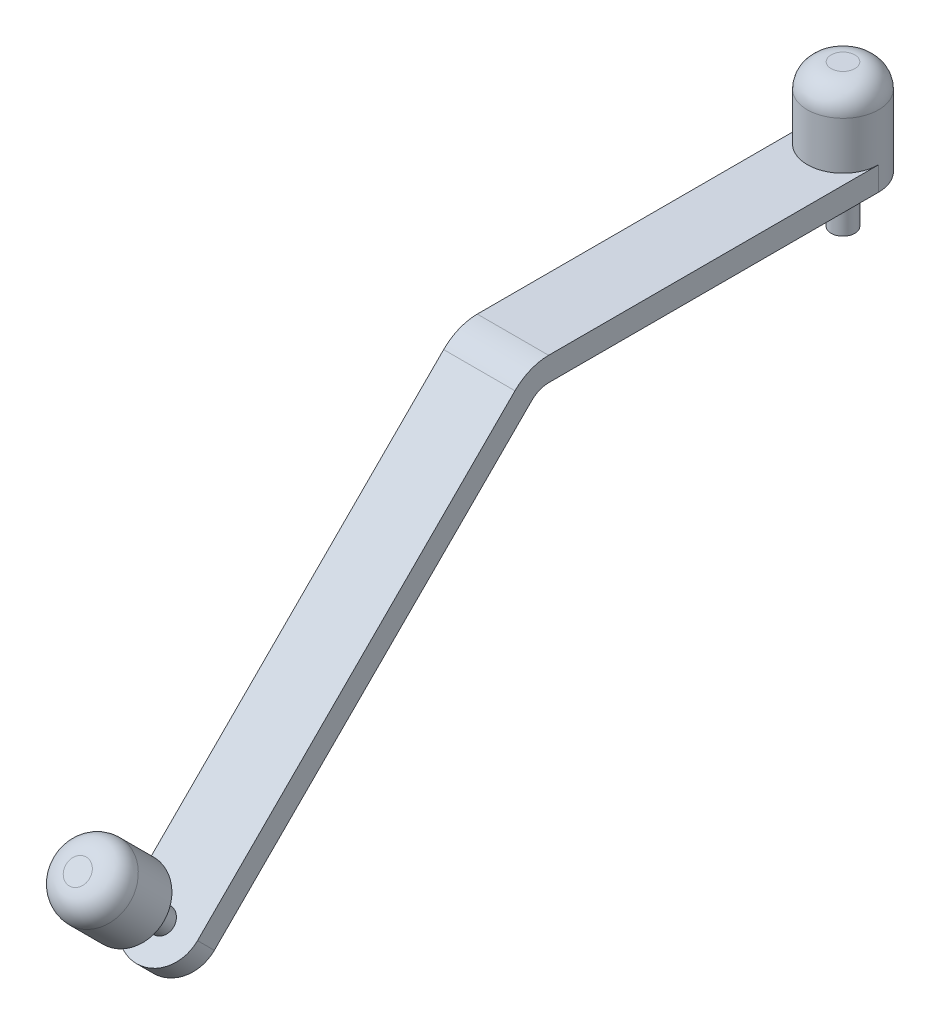
SolidWorks part; units mm, degrees
ref_plane "Front Plane" through (0, 0, 0) normal (0, 0, 1) x (1, 0, 0)
ref_plane "Top Plane" through (0, 0, 0) normal (0, 1, 0) x (1, 0, 0)
ref_plane "Right Plane" through (0, 0, 0) normal (1, 0, 0) x (0, 0, -1)
sketch "Sketch1" plane through (0, 0, 0) normal (1, 0, 0) x (0, 0, -1)
  line L0 (-80, 0) -> (-228.4924, -148.4924)
  line L1 (-80, -5) -> (80, -5)
  line L2 (-80, -5) -> (-80, 5)
  line L3 (-80, 5) -> (80, 5)
  line L4 (80, -5) -> (80, 5)
  line L5 (-80, -5) -> (80, 5) construction
  line L6 (-80, 5) -> (80, -5) construction
  line L7 (-232.028, -144.9569) -> (-83.5355, 3.5355)
  line L8 (-232.028, -144.9569) -> (-224.9569, -152.028)
  line L9 (-83.5355, 3.5355) -> (-76.4645, -3.5355)
  line L10 (-224.9569, -152.028) -> (-76.4645, -3.5355)
  line L11 (-232.028, -144.9569) -> (-76.4645, -3.5355) construction
  line L12 (-83.5355, 3.5355) -> (-224.9569, -152.028) construction
  line L13 (-83.5355, 3.5355) -> (-81.133, 5.9381)
  line L14 (-80, 5) -> (-82.0711, 5)
  point P0 (0, 0)
  point P8 (0, 0)
  point P9 (-154.2462, -74.2462)
extrude "Boss-Extrude1" add sketch "Sketch1" along normal blind 30 contours L10 L1 L4 L3 L2 L9 | L2 L9 | L9 L7 L8 L0 | L8 L10 L1 L2 L0 | L1 L10 L9 L2 region at (0, -76.7403, 153.2131) region at (0, -3.0893, 78.7204) region at (0, 3.0893, 81.2796) region at (0, -72.4784, 156.014) region at (0, 0.0201, -0.5128)
fillet "Fillet1" radius 10 1 edges at (15, -5, 77.9289)
fillet "Fillet2" radius 20 1 edges at (15, 5, 82.0711)
fillet "Fillet3" radius 15 2 edges at (30, -148.4924, 228.4924) (0, -148.4924, 228.4924)
fillet "Fillet4" radius 15 2 edges at (30, 0, -80) (0, 0, -80)
sketch "Sketch2" plane through (0, 43.5355, 43.5355) normal (0, 0.7071, 0.7071) x (1, 0, 0)
  circle A0 centre (15, -251.5685) radius 5
extrude "Boss-Extrude2" add sketch "Sketch2" along normal blind 20
sketch "Sketch3" plane through (0, 57.6777, 57.6777) normal (0, 0.7071, 0.7071) x (1, 0, 0)
  circle A0 centre (15, -251.5685) radius 15
extrude "Boss-Extrude3" add sketch "Sketch3" along normal blind 30
fillet "Fillet5" radius 10 1 edges at (15, -109.6016, 267.3833)
sketch "Sketch4" plane through (0, -5, 0) normal (0, -1, 0) x (1, 0, 0)
  circle A0 centre (15, -65) radius 5
extrude "Boss-Extrude4" add sketch "Sketch4" along normal blind 20
sketch "Sketch5" plane through (0, 5, 0) normal (0, 1, 0) x (1, 0, 0)
  circle A0 centre (15, 65) radius 15
extrude "Boss-Extrude5" add sketch "Sketch5" along normal blind 30
fillet "Fillet6" radius 10 1 edges at (15, 35, -50)
